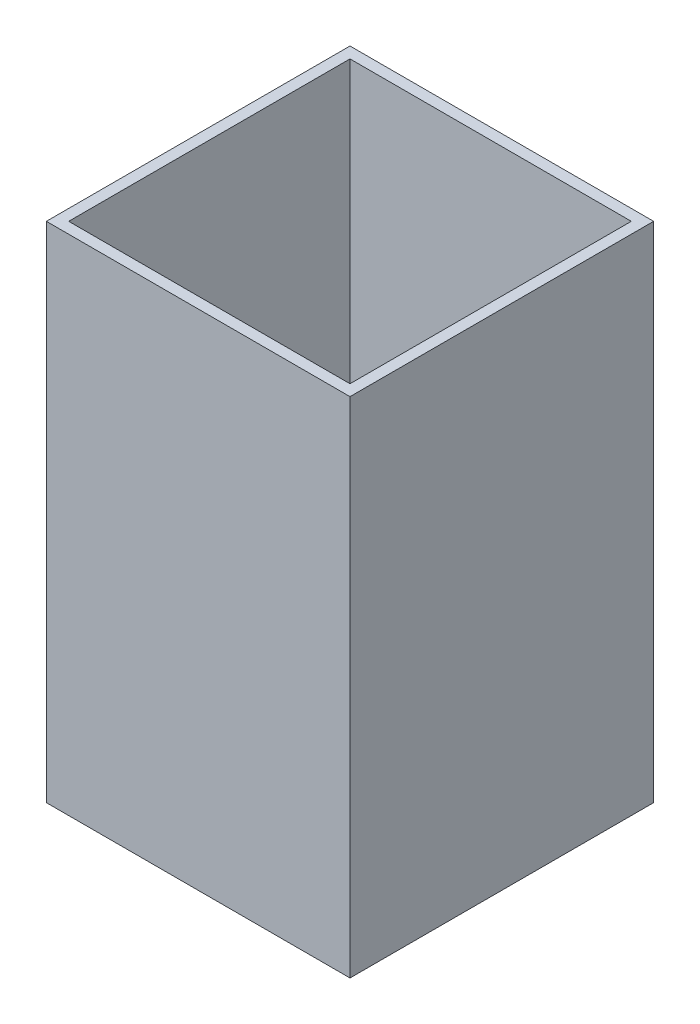
SolidWorks part; units mm, degrees
ref_plane "Front Plane" through (0, 0, 0) normal (0, 0, 1) x (1, 0, 0)
ref_plane "Top Plane" through (0, 0, 0) normal (0, 1, 0) x (1, 0, 0)
ref_plane "Right Plane" through (0, 0, 0) normal (1, 0, 0) x (0, 0, -1)
sketch "Sketch1" plane through (0, 0, 0) normal (0, 1, 0) x (1, 0, 0)
  line L1 (0, 0) -> (86.35, 0)
  line L2 (0, 0) -> (0, 86.35)
  line L3 (0, 86.35) -> (86.35, 86.35)
  line L4 (86.35, 0) -> (86.35, 86.35)
  line L5 (3.175, 3.175) -> (83.175, 3.175)
  line L6 (3.175, 3.175) -> (3.175, 83.175)
  line L7 (3.175, 83.175) -> (83.175, 83.175)
  line L8 (83.175, 3.175) -> (83.175, 83.175)
  line L9 (3.175, 83.175) -> (0, 83.175) construction
  line L10 (3.175, 83.175) -> (3.175, 86.35) construction
  line L11 (83.175, 3.175) -> (83.175, 0) construction
  line L12 (83.175, 3.175) -> (86.35, 3.175) construction
  point P9 (3.175, 100.1955)
  dimension "D1" = 80
  dimension "D2" = 3.175
extrude "Boss-Extrude1" add sketch "Sketch1" along normal blind 140
sketch "Sketch2" plane through (0, 0, 0) normal (0, -1, 0) x (1, 0, 0)
  line L1 (0, 0) -> (86.35, 0)
  line L2 (0, 0) -> (0, -86.35)
  line L3 (0, -86.35) -> (86.35, -86.35)
  line L4 (86.35, 0) -> (86.35, -86.35)
extrude "Boss-Extrude2" add sketch "Sketch2" along normal blind 3.175
